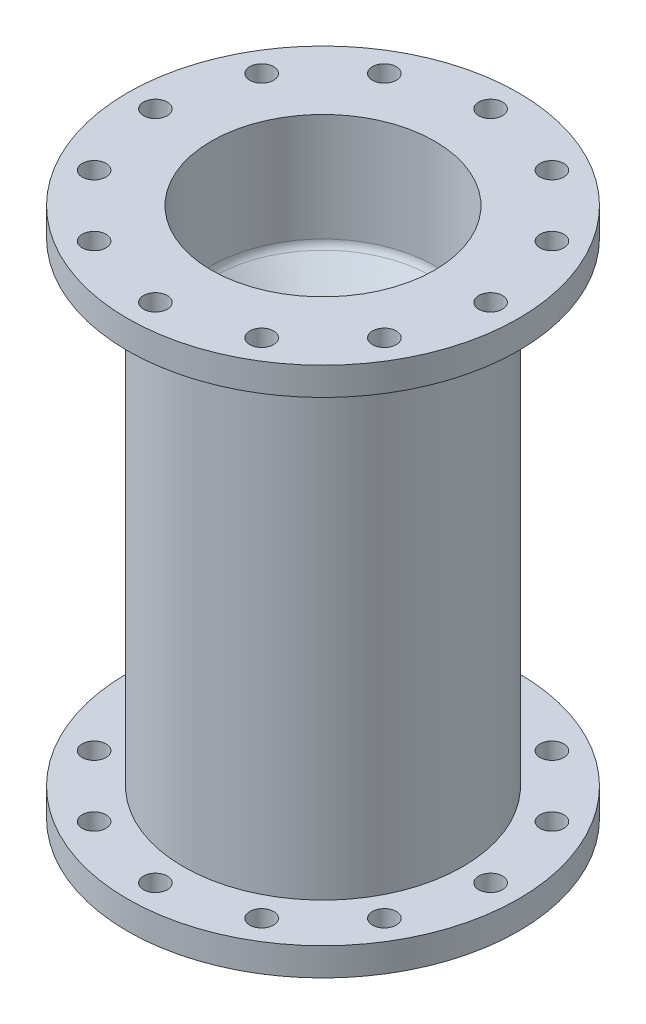
SolidWorks part; units mm, degrees
ref_plane "Front Plane" through (0, 0, 0) normal (0, 0, 1) x (1, 0, 0)
ref_plane "Top Plane" through (0, 0, 0) normal (0, 1, 0) x (1, 0, 0)
ref_plane "Right Plane" through (0, 0, 0) normal (1, 0, 0) x (0, 0, -1)
sketch "Sketch1" plane through (0, 0, 0) normal (1, 0, 0) x (0, 0, -1)
  line L1 (31.75, 6.35) -> (31.75, 114.3)
  line L8 (31.75, 120.65) -> (44.45, 120.65)
  line L9 (44.45, 120.65) -> (44.45, 114.3)
  line L10 (44.45, 114.3) -> (31.75, 114.3)
  line L11 (31.75, 0) -> (44.45, 0)
  line L12 (44.45, 0) -> (44.45, 6.35)
  line L13 (44.45, 6.35) -> (31.75, 6.35)
  line L27 (25.4, 114.3) -> (25.4, 120.65)
  line L28 (25.4, 120.65) -> (31.75, 120.65)
  line L29 (25.4, 6.35) -> (25.4, 0)
  line L30 (25.4, 0) -> (31.75, 0)
  line L31 (25.4, 114.3) -> (25.4, 6.35)
  line L32 (25.4, 0) -> (0, 0) construction
  line L33 (0, 0) -> (0, 6.35) construction
  dimension "D1" = 6.35
  dimension "D2" = 6.35
  dimension "D3" = 12.7
  dimension "D4" = 12.7
  dimension "D5" = 12.7
  dimension "D6" = 12.7
  dimension "D7" = 107.95
  dimension "D8" = 25.4
  dimension "D9" = 6.35
revolve "Chamber" add sketch "Sketch1" angle 360 about L33
sketch "Sketch4" plane through (0, 0, 0) normal (1, 0, 0) x (0, 0, -1)
  line L0 (0, 0) -> (0, 120.65) construction
  line L1 (25.4, 120.65) -> (-25.4, 120.65) construction
  line L8 (0, 60.325) -> (25.4, 60.325) construction
  line L15 (0, 0) -> (25.4, 0) construction
  line L16 (25.4, 0) -> (25.4, 86.5116) construction
  line L17 (25.4, 95.1837) -> (7.62, 95.1837) construction
  line L18 (7.62, 95.1837) -> (7.62, 77.4037) construction
  line L23 (24.6588, 94.4425) -> (7.62, 77.4037)
  line L24 (7.62, 77.4037) -> (7.62, 74.8637)
  line L25 (7.62, 74.8637) -> (21.0639, 88.3077)
  line L26 (25.4027, 96.2319) -> (25.4662, 120.5836) construction
  line L27 (0, 120.65) -> (25.4662, 120.5836) construction
  line L29 (25.4027, 96.2319) -> (25.4, 86.5116)
  arc A0 (25.4, 86.5116) -> (21.0639, 88.3077) centre (22.86, 86.5116) ccw
  arc A1 (25.4027, 96.2319) -> (24.6588, 94.4425) centre (22.8627, 96.2386) cw
  dimension "D5" = 2.54
  dimension "D6" = 2.54
  dimension "D2" = 25.4
  dimension "D1" = 7.62
  dimension "D3" = 25.4
  dimension "D4" = 2.54
revolve "Turbulence Rings" add sketch "Sketch4" angle 360 about L0
sketch "Sketch5" plane through (0, 120.65, 0) normal (0, 1, 0) x (1, 0, 0)
  line L0 (0, 0) -> (-38.1, 0) construction
  line L1 (0, 0) -> (-32.9956, 19.05) construction
  circle A0 centre (0, 0) radius 38.1 construction
  point P0 (0, 0)
  point P5 (-38.1, 0)
  point P9 (-32.9956, 19.05)
  point P10 (-19.05, 32.9956)
  point P11 (0, 38.1)
  point P12 (19.05, 32.9956)
  point P13 (32.9956, 19.05)
  point P14 (38.1, 0)
  point P15 (32.9956, -19.05)
  point P16 (19.05, -32.9956)
  point P17 (0, -38.1)
  point P18 (-19.05, -32.9956)
  point P19 (-32.9956, -19.05)
  point P20 (0, 0)
  point P21 (0, 0)
  point P24 (0, 0)
  point P26 (0, 0)
  dimension "D3" = 38.1
  dimension "D1" = 30
  dimension "D2" = 12
hole_wizard "#3 (0.213) Diameter Hole3" positions "Sketch5" profile "Sketch9" hole size "#3" standard "ANSI Inch" end condition through all
sketch "Sketch9" plane through (0, 120.65, 0) normal (1, 0, 0) x (0, 0, 1)
  line L0 (0, 0) -> (0, 120.65)
  line L1 (0, 120.65) -> (2.7051, 120.65)
  line L2 (2.7051, 120.65) -> (2.7051, 0)
  line L5 (2.7051, 0) -> (0, 0)
  line L11 (0, -6.35) -> (0, 107.95) construction
  dimension "Thru Hole Dia." = 5.4102
  dimension "Thru Hole Depth" = 120.65
equation "\"Thickness of Material\"= 0.3in"
equation "\"Chamber Length\"= 4.25in"
equation "\"Flange Length\"= 0.5in"
equation "\"Chamber Wall Thickness\"= 0.25in"
equation "\"Ring Length\"= 1.2in"
equation "\"Ring Thickness\"= 0.1in"
equation "\"Number of Rings\"= 2"
equation "\"Chamber Radius\"= 1in"
equation "\"D7@Sketch1\"= \"Chamber Length\""
equation "\"D9@Sketch1\"= \"Chamber Wall Thickness\""
equation "\"D8@Sketch1\"= \"Chamber Radius\""
equation "\"Flange Thickness\"= 0.25in"
equation "\"D1@Sketch1\"= \"Flange Thickness\""
equation "\"D3@Sketch5\"= \"Chamber Radius\" + \"Chamber Wall Thickness\" + ( \"Flange to Inner Wall Length\" / 2 )"
equation "\"Flange to Inner Wall Length\"= ( \"Chamber Radius\" + \"Chamber Wall Thickness\" + \"Flange Length\" ) - ( \"Chamber Radius\" + \"Chamber Wall Thickness\" )"
equation "\"D2@Sketch4\"= \"Chamber Radius\""
equation "\"Turbulence Ring Distance from Top\"= 1in"
equation "\"D4@Sketch1\"= \"Flange Length\""
equation "\"D3@Sketch1\"= \"Flange Length\""
equation "\"D5@Sketch1\"= \"Flange Length\""
equation "\"D6@Sketch1\"= \"Flange Length\""
equation "\"Center to Ring Edge Distance\"= 0.3 * ( \"Chamber Radius\" )"
equation "\"D1@Sketch4\"= \"Center to Ring Edge Distance\""
equation "\"D3@Sketch4\"= \"Turbulence Ring Distance from Top\""
equation "\"D4@Sketch4\"= \"Ring Thickness\""
